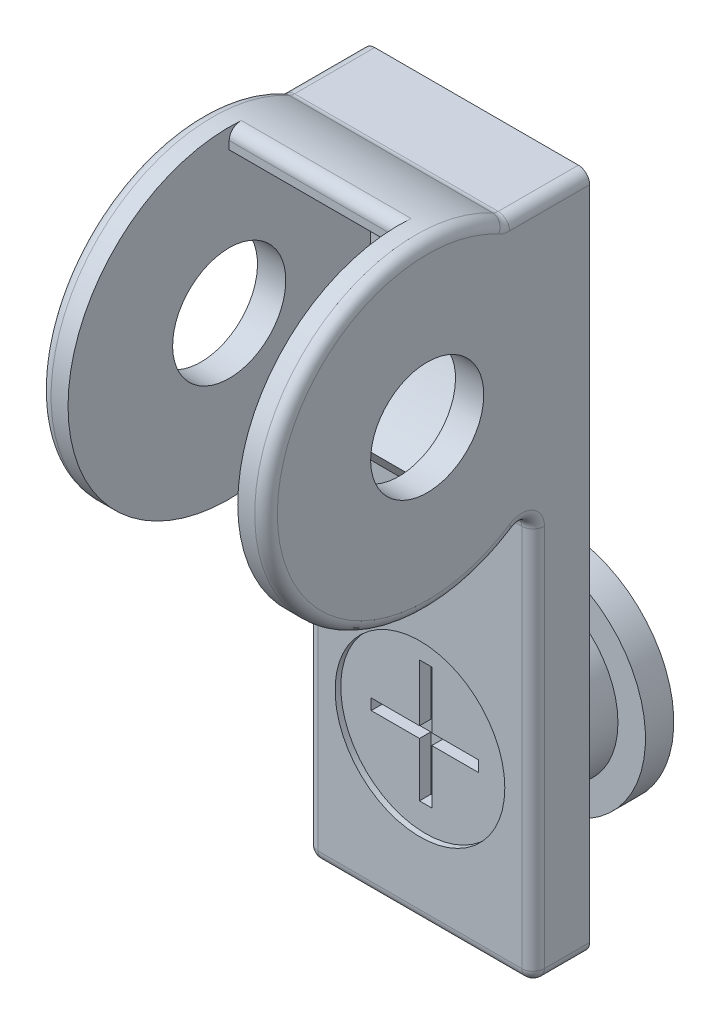
SolidWorks part; units mm, degrees
ref_plane "Front Plane" through (0, 0, 0) normal (0, 0, 1) x (1, 0, 0)
ref_plane "Top Plane" through (0, 0, 0) normal (0, 1, 0) x (1, 0, 0)
ref_plane "Right Plane" through (0, 0, 0) normal (1, 0, 0) x (0, 0, -1)
sketch "Sketch1" plane through (0, 0, 0) normal (0, 0, 1) x (1, 0, 0)
  line L1 (-2, 7.5) -> (2, 7.5)
  line L2 (-2, 7.5) -> (-2, -7.5)
  line L3 (-2, -7.5) -> (2, -7.5)
  line L4 (2, 7.5) -> (2, -7.5)
  line L5 (-2, 7.5) -> (2, -7.5) construction
  line L6 (-2, -7.5) -> (2, 7.5) construction
  point P0 (0, 0)
extrude "Boss-Extrude1" add sketch "Sketch1" along normal blind 1
sketch "Sketch2" plane through (0, 0, 1) normal (0, 0, 1) x (1, 0, 0)
  circle A0 centre (0, -5.0013) radius 1.5
  circle A1 centre (0, -1.6839) radius 1.5
extrude "Cut-Extrude1" cut sketch "Sketch2" against normal blind 0.1
sketch "Sketch3" plane through (0, 0, 0.9) normal (0, 0, 1) x (1, 0, 0)
  line L0 (0, -3.1839) -> (0, -3.5013) construction
  line L1 (-0.1086, -6.1071) -> (0.1086, -6.1071)
  line L2 (-0.1086, -6.1071) -> (-0.1086, -5.0983)
  line L3 (-0.1086, -3.9486) -> (0.1086, -3.9486)
  line L4 (0.1086, -6.1071) -> (0.1086, -5.0983)
  line L7 (0.9335, -4.9042) -> (0.1086, -4.9042)
  line L8 (0.9335, -4.9042) -> (0.9335, -5.0983)
  line L9 (0.9335, -5.0983) -> (0.1086, -5.0983)
  line L10 (-0.962, -4.9042) -> (-0.962, -5.0983)
  line L13 (-0.5313, -3.3426) -> (0.8099, -3.3426) construction
  line L14 (-0.1086, -5.0983) -> (-0.962, -5.0983)
  line L16 (-0.1086, -4.9042) -> (-0.1086, -3.9486)
  line L17 (0.1086, -4.9042) -> (0.1086, -3.9486)
  line L18 (-0.962, -1.7809) -> (-0.962, -1.5869)
  line L19 (0.9335, -1.5869) -> (0.1086, -1.5869)
  line L20 (0.9335, -1.7809) -> (0.9335, -1.5869)
  line L21 (0.9335, -1.7809) -> (0.1086, -1.7809)
  line L22 (0.1086, -0.5781) -> (0.1086, -1.5869)
  line L23 (-0.1086, -2.7365) -> (0.1086, -2.7365)
  line L24 (-0.1086, -0.5781) -> (-0.1086, -1.5869)
  line L25 (-0.1086, -0.5781) -> (0.1086, -0.5781)
  line L26 (-0.1086, -4.9042) -> (-0.962, -4.9042)
  line L30 (-0.1086, -1.5869) -> (-0.962, -1.5869)
  line L31 (-0.1086, -1.7809) -> (-0.962, -1.7809)
  line L32 (-0.1086, -1.7809) -> (-0.1086, -2.7365)
  line L33 (0.1086, -1.7809) -> (0.1086, -2.7365)
  circle A0 centre (0, -1.6839) radius 1.5 construction
  circle A1 centre (0, -1.6839) radius 1.5 construction
  circle A2 centre (0, -5.0013) radius 1.5 construction
  point P0 (0, -5.0013)
  point P6 (0, -5.0013)
  point P30 (0, -1.6839)
extrude "Cut-Extrude2" cut sketch "Sketch3" against normal blind 0.2
sketch "Sketch4" plane through (2, 0, 0) normal (1, 0, 0) x (0, 0, -1)
  circle A0 centre (-2.872, 5.0208) radius 2.849
extrude "Boss-Extrude2" add sketch "Sketch4" against normal up to surface (4 mm away) up to face at (-2, 0, 0.5)
sketch "Sketch5" plane through (2, 0, 0) normal (1, 0, 0) x (0, 0, -1)
  line L0 (-2.872, 7.2) -> (-2.872, 9.2971)
  line L1 (-1.7612, 3.1459) -> (-1.262, 2.3033)
  line L2 (-1.262, 2.3033) -> (-10.3597, 0.939)
  line L3 (-10.3597, 0.939) -> (-14.7671, 7.4504)
  line L4 (-14.7671, 7.4504) -> (-2.872, 9.2971)
  arc A0 (-1.7612, 3.1459) -> (-2.872, 7.2) centre (-2.872, 5.0208) ccw
extrude "Cut-Extrude3" cut sketch "Sketch5" against normal offset from surface (3 mm away) 0.5 from offset 0.5 up to face at (-2, 1.6736, 1.4535) offset against normal yes
sketch "Sketch6" plane through (2, 0, 0) normal (1, 0, 0) x (0, 0, -1)
  circle A0 centre (-2.872, 5.0208) radius 1
extrude "Cut-Extrude4" cut sketch "Sketch6" against normal blind 50.5
sketch "Sketch7" plane through (0, 0, 1) normal (0, 0, 1) x (1, 0, 0)
  line L4 (-2, 7.1685) -> (2, 7.1685)
  line L5 (2, 7.1685) -> (2, 7.5)
  line L6 (2, 7.5) -> (-2, 7.5)
  line L7 (-2, 7.5) -> (-2, 7.1685)
  line L8 (-2, 7.1685) -> (2, 7.1685)
  line L9 (2, 7.1685) -> (2, 7.5)
  line L10 (2, 7.5) -> (-2, 7.5)
  line L11 (-2, 7.5) -> (-2, 7.1685)
  dimension "D1" = 0
extrude "Boss-Extrude3" add sketch "Sketch7" along normal up to surface (0.4683 mm away) up to face at (0, 4.7438, 3.8828)
sketch "Sketch8" plane through (0, 0, 0) normal (0, 0, -1) x (-1, 0, 0)
  circle A0 centre (0, -1.6839) radius 1.5 construction
  circle A1 centre (0, -5.0013) radius 1.5 construction
  circle A2 centre (0, -1.6839) radius 1.5
  circle A3 centre (0, -5.0013) radius 1.5
extrude "Boss-Extrude4" add sketch "Sketch8" along normal blind 1.5
sketch "Sketch13" plane through (-1.5, 0, 0) normal (1, 0, 0) x (0, 0, -1)
  circle A0 centre (-2.872, 5.0208) radius 2.5
extrude "Cut-Extrude6" cut sketch "Sketch13" along normal blind 3
sketch "Sketch14" plane through (0, 0, 1) normal (0, 0, 1) x (1, 0, 0)
  circle A0 centre (0, -5.0013) radius 1.5
  circle A1 centre (0, -5.0013) radius 1.5 construction
extrude "Boss-Extrude5" add sketch "Sketch14" against normal blind 1
sketch "Sketch15" plane through (0, 0, -1.5) normal (0, 0, -1) x (-1, 0, 0)
  circle A0 centre (0, -5.0013) radius 1.6551
extrude "Cut-Extrude7" cut sketch "Sketch15" against normal up to surface (1.5 mm away) up to face at (1.5, -5.0013, 0)
sketch "Sketch16" plane through (0, -7.5, 0) normal (0, -1, 0) x (1, 0, 0)
  line L1 (-2.3443, 1.5021) -> (2.7554, 1.5021)
  line L2 (-2.3443, 1.5021) -> (-2.3443, -0.7167)
  line L3 (-2.3443, -0.7167) -> (2.7554, -0.7167)
  line L4 (2.7554, 1.5021) -> (2.7554, -0.7167)
  line L5 (-2.3443, 1.5021) -> (2.7554, -0.7167) construction
  line L6 (-2.3443, -0.7167) -> (2.7554, 1.5021) construction
  point P0 (0.2056, 0.3927)
extrude "Cut-Extrude8" cut sketch "Sketch16" against normal blind 3
fillet "Fillet1" radius 0.2 12 edges at (0, 7.8698, 2.872) (0, 7.5, 1.4683) (2, 7.5, 0.7342) (-2, 7.5, 0.7342) (0, 2.8731, 1) (2, 4.7339, 5.7065) (-2, 4.7339, 5.7065) (2, -4.5, 0.5) (-2, -4.5, 0.5) (2, -0.8135, 1) (0, -4.5, 1) (-2, -0.8135, 1)
sketch "Sketch17" plane through (0, 0, 0) normal (0, 0, -1) x (-1, 0, 0)
  line L0 (0, 7.5) -> (0, 0.7087) construction
  line L1 (-1.8, 7.5) -> (1.8, 7.5) construction
  circle A0 centre (0, 4.363) radius 1.2887
extrude "Boss-Extrude6" add sketch "Sketch17" along normal blind 1
fillet "Fillet2" radius 1 1 edges at (-1.2887, 4.363, -1)
sketch "Sketch18" plane through (0, 0, -1.5) normal (0, 0, -1) x (-1, 0, 0)
  circle A0 centre (0, -1.6839) radius 1.9866
extrude "Boss-Extrude7" add sketch "Sketch18" against normal blind 0.5
equation "\"z\"=11.2"
